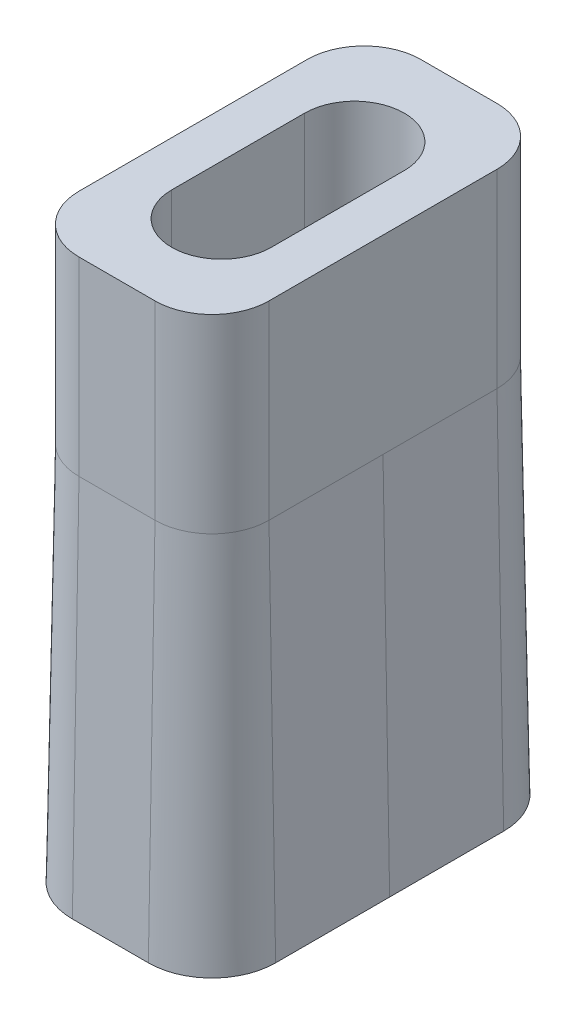
SolidWorks part; units mm, degrees
material "K110"
ref_plane "Front Plane" through (0, 0, 0) normal (0, 0, 1) x (1, 0, 0)
ref_plane "Top Plane" through (0, 0, 0) normal (0, 1, 0) x (1, 0, 0)
ref_plane "Right Plane" through (0, 0, 0) normal (1, 0, 0) x (0, 0, -1)
sketch "Sketch1" plane through (0, 0, 0) normal (0, 1, 0) x (1, 0, 0)
  line L3 (0, -3.5) -> (0, 3.5) construction
  line L4 (-2.62, -3.5) -> (-2.62, 3.5) construction
  line L5 (2.62, -3.5) -> (2.62, 3.5) construction
  line L6 (-2, -9) -> (2, -9)
  line L7 (-5, -6) -> (-5, 6)
  line L8 (-2, 9) -> (2, 9)
  line L9 (5, -6) -> (5, 6)
  line L10 (-5, -9) -> (5, 9) construction
  line L11 (-5, 9) -> (5, -9) construction
  arc A2 (-2.62, -3.5) -> (2.62, -3.5) centre (0, -3.5) ccw construction
  arc A3 (2.62, 3.5) -> (-2.62, 3.5) centre (0, 3.5) ccw construction
  arc A4 (-2, -9) -> (-5, -6) centre (-2, -6) cw
  arc A5 (2, -9) -> (5, -6) centre (2, -6) ccw
  arc A6 (2, 9) -> (5, 6) centre (2, 6) cw
  arc A7 (-5, 6) -> (-2, 9) centre (-2, 6) cw
  point P0 (0, 0)
  point P10 (0, 0)
  dimension "D1" = 7
  dimension "D3" = 2.62
  dimension "D5" = 3
  dimension "D2" = 18
  dimension "D4" = 10
extrude "Boss-Extrude1" add sketch "Sketch1" against normal blind 30
sketch "Sketch5" plane through (0, 0, 0) normal (0, 1, 0) x (1, 0, 0)
  line L0 (0, -3.5) -> (0, 3.5) construction
  line L1 (-2.62, -3.5) -> (-2.62, 3.5)
  line L2 (2.62, -3.5) -> (2.62, 3.5)
  arc A0 (-2.62, -3.5) -> (2.62, -3.5) centre (0, -3.5) ccw
  arc A1 (2.62, 3.5) -> (-2.62, 3.5) centre (0, 3.5) ccw
  point P4 (0, 0)
  point P9 (0, 0)
extrude "Cut-Extrude2" cut sketch "Sketch5" against normal up to next
sketch "Sketch6" plane through (0, 0, 0) normal (0, 0, 1) x (1, 0, 0)
  line L0 (5, -10) -> (5.3491, -30)
  line L1 (5, -30) -> (5, 0) construction
  line L2 (5.3491, -30) -> (5, -30)
  line L3 (5, -30) -> (5, -10)
  line L4 (5.884, 0) -> (-5.884, 0) construction
  dimension "D1" = 10
  dimension "D2" = 1
sweep "Sweep1" add profiles "Sketch6" path "Sketch1<3>"
sketch "Sketch1<3>" plane through (0, 0, 0) normal (0, 1, 0) x (1, 0, 0) same geometry as "Sketch1"
